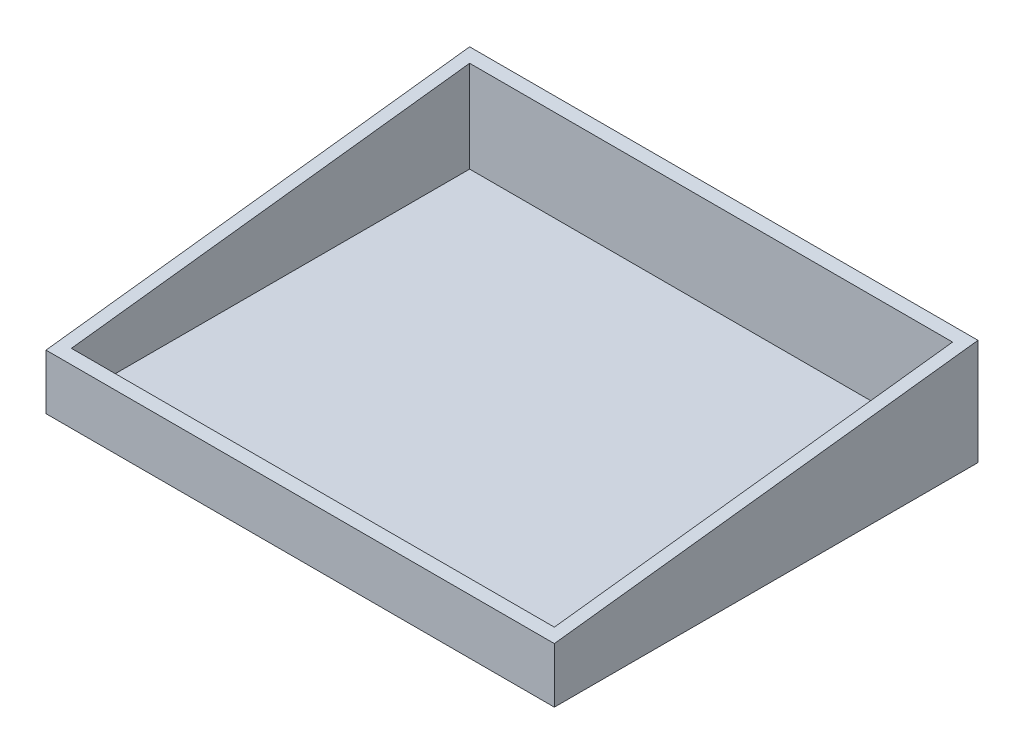
SolidWorks part; units mm, degrees
ref_plane "Front Plane" through (0, 0, 0) normal (0, 0, 1) x (1, 0, 0)
ref_plane "Top Plane" through (0, 0, 0) normal (0, 1, 0) x (1, 0, 0)
ref_plane "Right Plane" through (0, 0, 0) normal (1, 0, 0) x (0, 0, -1)
sketch "Sketch1" plane through (0, 0, 0) normal (0, 1, 0) x (1, 0, 0)
  line L1 (0, 0) -> (120, 0)
  line L2 (0, 0) -> (0, 100)
  line L3 (0, 100) -> (120, 100)
  line L4 (120, 0) -> (120, 100)
  dimension "D1" = 120
  dimension "D2" = 100
extrude "Boss-Extrude1" add sketch "Sketch1" along normal blind 25
sketch "Sketch2" plane through (120, 0, 0) normal (1, 0, 0) x (0, 0, -1)
  line L0 (0, 13) -> (0, 25)
  line L1 (0, 25) -> (0, 0) construction
  line L2 (0, 25) -> (100, 25)
  line L3 (100, 25) -> (0, 13)
  dimension "D1" = 12
extrude "Cut-Extrude1" cut sketch "Sketch2" against normal through all and the other way through all
shell "Shell1" thickness 3 removed face at (75, 20.5, -62.5)
